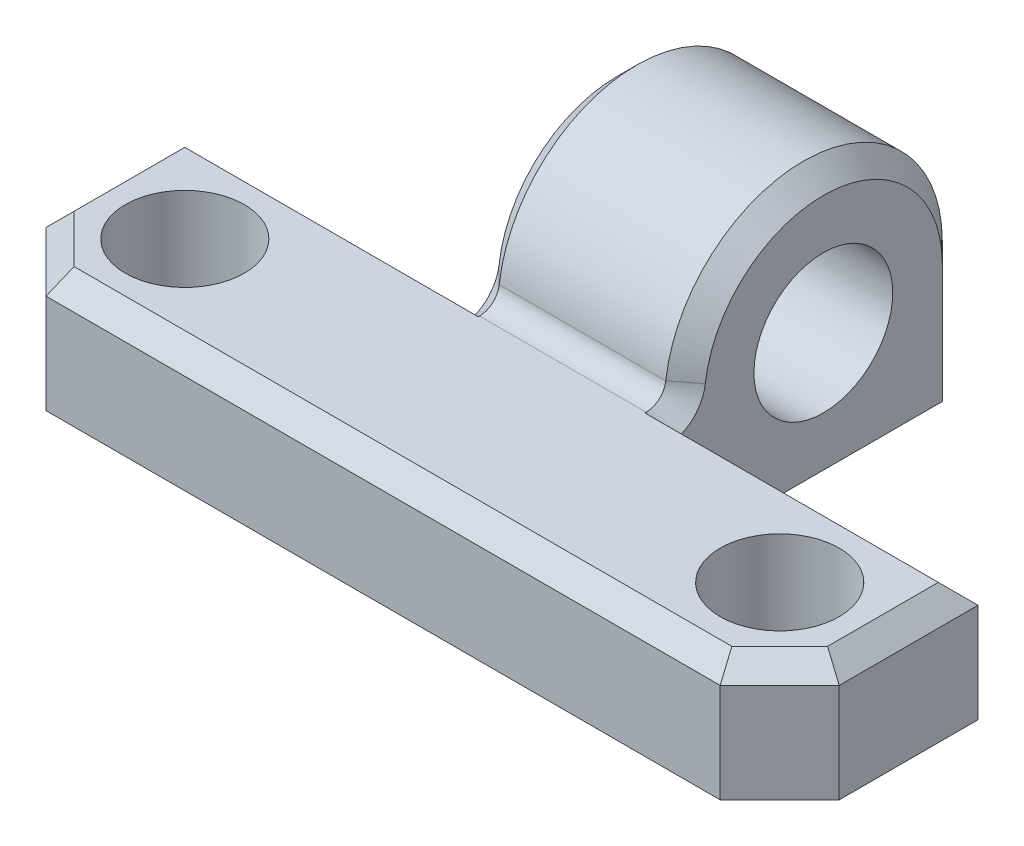
SolidWorks part; units mm, degrees
ref_plane "Vorne" through (0, 0, 0) normal (0, 0, 1) x (1, 0, 0)
ref_plane "Oben" through (0, 0, 0) normal (0, 1, 0) x (1, 0, 0)
ref_plane "Rechts" through (0, 0, 0) normal (1, 0, 0) x (0, 0, -1)
sketch "Skizze1" plane through (0, 0, 0) normal (0, 1, 0) x (1, 0, 0)
  line L1 (10, 6) -> (-10, 6)
  line L2 (10, 6) -> (10, -6)
  line L3 (10, -6) -> (-10, -6)
  line L4 (-10, 6) -> (-10, -6)
  line L5 (10, 6) -> (-10, -6) construction
  line L6 (10, -6) -> (-10, 6) construction
  point P0 (0, 0)
  dimension "D1" = 12
  dimension "D2" = 20
extrude "Aufsatz-Linear austragen1" add sketch "Skizze1" along normal blind 3
sketch "Skizze2" plane through (0, 3, 0) normal (0, 1, 0) x (1, 0, 0)
  line L0 (-10, 6) -> (-10, -6) construction
  line L1 (-10, -6) -> (10, -6) construction
  line L2 (0, -55) -> (0, 55) construction
  circle A0 centre (-7.5, -3.5) radius 1.5
  circle A1 centre (7.5, -3.5) radius 1.5
  dimension "D1" = 3
  dimension "D2" = 2.5
  dimension "D3" = 2.5
extrude "Schnitt-Linear austragen1" cut sketch "Skizze2" against normal up to next
sketch "Skizze3" plane through (-10, 0, 0) normal (-1, 0, 0) x (0, 0, 1)
  line L0 (-6, 3) -> (6, 3) construction
  line L1 (-6, 3) -> (1, 3)
  arc A0 (1, 3) -> (-6, 3) centre (-2.5, 3) ccw
  dimension "D1" = 7
  dimension "D2" = 2.5
  dimension "D3" = 0
extrude "Aufsatz-Linear austragen2" add sketch "Skizze3" against normal up to vertex (20 mm away) contours A0 L1 up to point (10, 3, -6)
chamfer "Fase1" distance 1.5 angle 45 2 edges at (10, 1.5, 6) (-10, 1.5, 6)
sketch "Skizze4" plane through (-10, 0, 0) normal (-1, 0, 0) x (0, 0, 1)
  circle A0 centre (-2.5, 3) radius 1.75
  arc A1 (1, 3) -> (-6, 3) centre (-2.5, 3) ccw construction
  dimension "D1" = 3.5
extrude "Schnitt-Linear austragen2" cut sketch "Skizze4" against normal through all
sketch "Skizze5" plane through (0, 0, 0) normal (0, 1, 0) x (1, 0, 0)
  line L0 (-10, 6) -> (-10, -1) construction
  line L1 (-10, 6) -> (-2.6, 6)
  line L2 (-10, 6) -> (-10, -1)
  line L3 (-10, -1) -> (-2.6, -1)
  line L4 (-2.6, 6) -> (-2.6, -1)
  line L5 (-10, 6) -> (-2.6, -1) construction
  line L6 (-10, -1) -> (-2.6, 6) construction
  line L8 (10, 6) -> (-10, 6) construction
  line L9 (0, -3.575) -> (0, 3.575) construction
  line L10 (10, -1) -> (2.6, -1)
  line L11 (10, 6) -> (2.6, 6)
  line L12 (10, 6) -> (10, -1)
  line L13 (2.6, 6) -> (2.6, -1)
  point P0 (-6.3, 2.5)
  point P7 (0, 0)
  dimension "D1" = 7.4
  dimension "D2" = 0
  dimension "D3" = 3.5
  dimension "D4" = 7
extrude "Schnitt-Linear austragen5" cut sketch "Skizze5" along normal through all
chamfer "Fase2" distance 0.5 angle 45 7 edges at (-6.3, 3, 1) (6.3, 3, 1) (10, 3, 2.75) (9.25, 3, 5.25) (0, 3, 6) (-9.25, 3, 5.25) (-10, 3, 2.75)
fillet "Verrundung1" radius 0.5 1 edges at (0, 3, 1)
chamfer "Fase3" distance 0.5 angle 45 8 edges at (2.6, 3, 1.4843) (2.6, 3.125, 1.1379) (2.6, 1.5, -6) (2.6, 6.4931, -2.7192) (-2.6, 3, 1.4843) (-2.6, 1.5, -6) (-2.6, 3.125, 1.1379) (-2.6, 6.4931, -2.7192)
